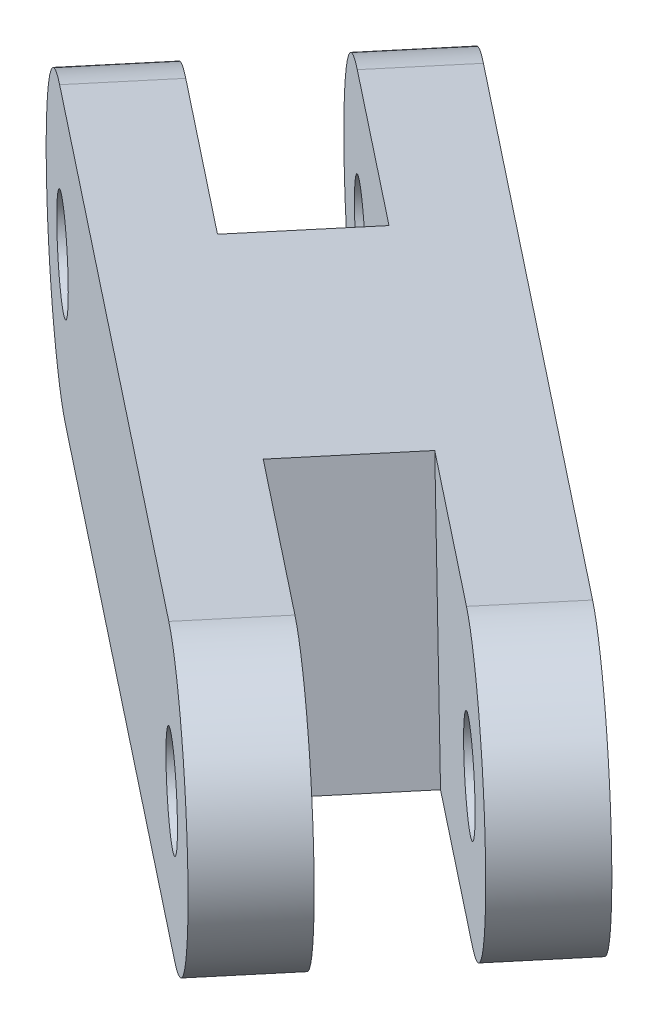
SolidWorks part; units mm, degrees
ref_plane "Front Plane" through (0, 0, 0) normal (0, 0, 1) x (1, 0, 0)
ref_plane "Top Plane" through (0, 0, 0) normal (0, 1, 0) x (1, 0, 0)
ref_plane "Right Plane" through (0, 0, 0) normal (1, 0, 0) x (0, 0, -1)
ref_plane "Plane1" through (10.7022, 0, -12.7544) normal (-0.6428, 0, 0.766) x (0.766, 0, 0.6428)
sketch "Sketch1" plane through (10.7022, 0, -12.7544) normal (-0.6428, 0, 0.766) x (0.766, 0, 0.6428)
  line L0 (-32.692, 7.7927) -> (-1.2779, 13.4367)
  line L1 (-31.0301, -1.4572) -> (0.384, 4.1868)
  circle A0 centre (-0.4469, 8.8117) radius 4.699 construction
  circle A1 centre (-31.861, 3.1677) radius 4.699 construction
  arc A2 (-32.692, 7.7927) -> (-31.0301, -1.4572) centre (-31.861, 3.1677) ccw
  arc A3 (-1.2779, 13.4367) -> (0.384, 4.1868) centre (-0.4469, 8.8117) cw
  circle A4 centre (-31.861, 3.1677) radius 1.651
  circle A5 centre (-0.4469, 8.8117) radius 1.651
  dimension "D1" = 9.398
  dimension "D2" = 9.398
  dimension "D4" = 3.302
  dimension "D5" = 3.302
  dimension "D3" = 9.398
extrude "Boss-Extrude1" add sketch "Sketch1" along normal blind 5.334 and the other way blind 5.334
sketch "Sketch3" plane through (-1.8221, 13.2389, -1.5289) normal (-0.1355, 0.9842, -0.1137) x (0.9908, 0.1346, -0.0155)
  line L0 (-19.6721, 31.6409) -> (-9.0411, 22.5776) construction
  line L1 (8.1923, 7.8856) -> (-16.0962, 28.5923) construction
  line L2 (-17.6122, 34.057) -> (-6.9812, 24.9937)
  line L3 (-12.751, 39.7591) -> (-2.12, 30.6958) construction
  line L4 (15.1133, 16.0038) -> (-9.1751, 36.7105) construction
  line L5 (-14.8108, 37.343) -> (-4.1799, 28.2797)
  line L7 (-17.6122, 34.057) -> (-14.8108, 37.343)
  line L8 (2.9691, 26.3572) -> (-3.952, 18.239) construction
  line L10 (16.6294, 10.5391) -> (5.9984, 19.6024)
  line L11 (13.828, 7.2531) -> (3.197, 16.3164)
  line L12 (13.828, 7.2531) -> (16.6294, 10.5391)
  line L13 (-6.9812, 24.9937) -> (-4.1799, 28.2797)
  line L14 (5.9984, 19.6024) -> (3.197, 16.3164)
  dimension "D1" = 3.175
  dimension "D2" = 3.175
extrude "Cut-Extrude1" cut sketch "Sketch3" against normal blind 10.414
